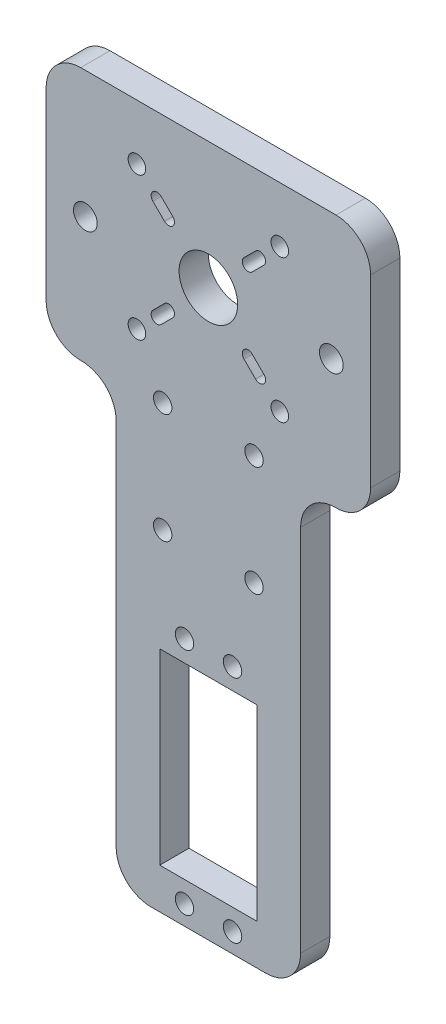
SolidWorks part; units mm, degrees
ref_plane "Front Plane" through (0, 0, 0) normal (0, 0, 1) x (1, 0, 0)
ref_plane "Top Plane" through (0, 0, 0) normal (0, 1, 0) x (1, 0, 0)
ref_plane "Right Plane" through (0, 0, 0) normal (1, 0, 0) x (0, 0, -1)
sketch "Sketch1" plane through (0, 0, 0) normal (0, 0, 1) x (1, 0, 0)
  line L0 (0, 0) -> (0, 11.938) construction
  line L3 (-20, -84) -> (20, -84)
  line L5 (-21.209, 78.74) -> (21.209, -78.74) construction
  line L6 (-21.209, -78.74) -> (21.209, 78.74) construction
  line L7 (0, 11.938) -> (9.906, 11.938) construction
  line L8 (0, 0) -> (0, 38.5) construction
  line L9 (0, 38.5) -> (15.494, 38.5) construction
  line L10 (15.494, 38.5) -> (15.494, 53.994) construction
  line L11 (0, 38.5) -> (9.8783, 48.3783) construction
  line L12 (8.621, 47.121) -> (11.1355, 49.6355) construction
  line L13 (7.723, 48.0191) -> (10.2375, 50.5335)
  line L14 (9.5191, 46.223) -> (12.0335, 48.7375)
  line L17 (8.621, 29.879) -> (11.1355, 27.3645) construction
  line L24 (0, 0) -> (0, -30) construction
  line L25 (0, -30) -> (-5.1689, -30) construction
  line L26 (0, -30) -> (0, -54.892) construction
  line L27 (0, 38.5) -> (-26.67, 38.5) construction
  line L28 (-10.541, -34.572) -> (10.541, -34.572)
  line L29 (-10.541, -34.572) -> (-10.541, -75.212)
  line L30 (-10.541, -75.212) -> (10.541, -75.212)
  line L31 (10.541, -34.572) -> (10.541, -75.212)
  line L32 (-10.541, -34.572) -> (10.541, -75.212) construction
  line L33 (-10.541, -75.212) -> (10.541, -34.572) construction
  line L40 (-20, 11) -> (-20, -84)
  line L41 (-35.179, 11) -> (-20, 11)
  line L42 (-35.179, 11) -> (-35.179, 66)
  line L43 (-35.179, 66) -> (35.179, 66)
  line L44 (35.179, 11) -> (35.179, 66)
  line L45 (-35.179, 11) -> (35.179, 66) construction
  line L46 (-35.179, 66) -> (35.179, 11) construction
  line L47 (20, 11) -> (20, -84)
  line L48 (20, 11) -> (35.179, 11)
  line L67 (9.5191, 30.777) -> (12.0335, 28.2625)
  line L70 (7.723, 28.9809) -> (10.2375, 26.4665)
  line L73 (-8.621, 29.879) -> (-11.1355, 27.3645) construction
  line L74 (-7.723, 28.9809) -> (-10.2375, 26.4665)
  line L75 (-9.5191, 30.777) -> (-12.0335, 28.2625)
  line L76 (-8.621, 47.121) -> (-11.1355, 49.6355) construction
  line L77 (-9.5191, 46.223) -> (-12.0335, 48.7375)
  line L78 (-7.723, 48.0191) -> (-10.2375, 50.5335)
  circle A0 centre (9.906, 11.938) radius 2
  circle A1 centre (-9.906, 11.938) radius 2
  circle A2 centre (-9.906, -11.938) radius 2
  circle A3 centre (9.906, -11.938) radius 2
  circle A4 centre (0, 38.5) radius 6.35
  circle A5 centre (15.494, 53.994) radius 1.905
  arc A9 (7.723, 48.0191) -> (9.5191, 46.223) centre (8.621, 47.121) ccw
  arc A10 (12.0335, 48.7375) -> (10.2375, 50.5335) centre (11.1355, 49.6355) ccw
  circle A17 centre (-5.1689, -30) radius 2
  circle A18 centre (5.2451, -30) radius 2
  circle A19 centre (5.2451, -79.784) radius 2
  circle A20 centre (-5.1689, -79.784) radius 2
  circle A21 centre (-26.67, 38.5) radius 2.575
  circle A28 centre (26.67, 38.5) radius 2.575
  circle A73 centre (15.494, 23.006) radius 1.905
  arc A74 (9.5191, 30.777) -> (7.723, 28.9809) centre (8.621, 29.879) ccw
  arc A75 (10.2375, 26.4665) -> (12.0335, 28.2625) centre (11.1355, 27.3645) ccw
  circle A76 centre (-15.494, 23.006) radius 1.905
  arc A77 (-7.723, 28.9809) -> (-9.5191, 30.777) centre (-8.621, 29.879) ccw
  arc A78 (-12.0335, 28.2625) -> (-10.2375, 26.4665) centre (-11.1355, 27.3645) ccw
  circle A79 centre (-15.494, 53.994) radius 1.905
  arc A80 (-9.5191, 46.223) -> (-7.723, 48.0191) centre (-8.621, 47.121) ccw
  arc A81 (-10.2375, 50.5335) -> (-12.0335, 48.7375) centre (-11.1355, 49.6355) ccw
  point P0 (0, 0)
  point P30 (9.8783, 48.3783)
  point P39 (9.8783, 28.6217)
  point P48 (-9.8783, 28.6217)
  point P57 (-9.8783, 48.3783)
  point P76 (0, 38.5)
  point P83 (-27.5895, 11)
  dimension "D3" = 4
  dimension "D6" = 12.7
  dimension "D9" = 3.81
  dimension "D15" = 1.27
  dimension "D27" = 4
  dimension "D30" = 5.15
  dimension "D11" = 55
  dimension "D31" = 9.906
  dimension "D1" = 11.938
  dimension "D2" = 9.906
  dimension "D5" = 38.5
  dimension "D7" = 15.494
  dimension "D8" = 15.494
  dimension "D13" = 95
  dimension "D14" = 45
  dimension "D16" = 1.778
  dimension "D17" = 13.97
  dimension "D19" = 30
  dimension "D20" = 5.1689
  dimension "D23" = 24.892
  dimension "D24" = 40.64
  dimension "D25" = 21.082
  dimension "D28" = 70.358
  dimension "D29" = 26.67
  dimension "D32" = 11.938
  dimension "D12" = 40
  dimension "D26" = 2
  dimension "D4" = 2
  dimension "D21" = 2
  dimension "D22" = 2
  dimension "D10" = 4
extrude "Boss-Extrude1" add sketch "Sketch1" along normal mid plane 6.35 contours A20 L3 A19 L47 L48 L44 L43 L42 L41 L40 A81 L78 A80 L77 A79 A78 L75 A77 L74 A76 A75 L70 A74 L67 A73 L28 L31 L30 L29 A0 A1 A2 A3 A4 A5 region at (-0.0003, 7.7094, 0)
fillet "Fillet1" radius 7.5 8 edges at (-20, -84, 0) (20, -84, 0) (20, 11, 0) (35.179, 11, 0) (35.179, 66, 0) (-20, 11, 0) (-35.179, 11, 0) (-35.179, 66, 0)
